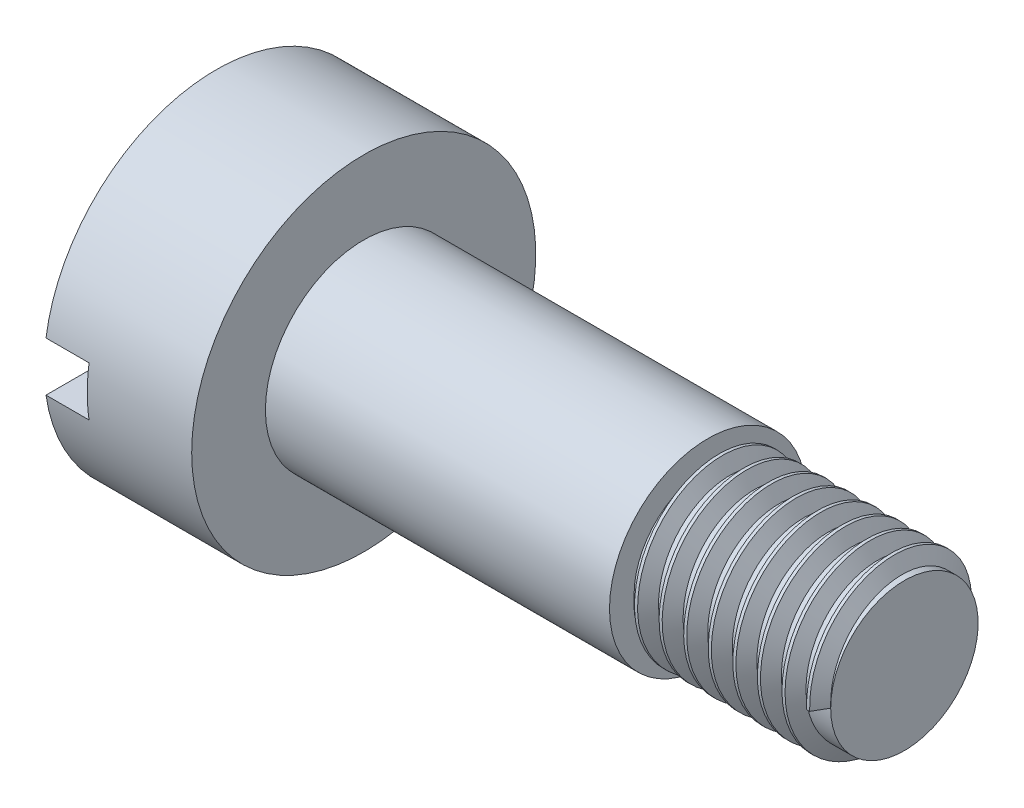
SolidWorks part; units mm, degrees
ref_plane "Front Plane" through (0, 0, 0) normal (0, 0, 1) x (1, 0, 0)
ref_plane "Top Plane" through (0, 0, 0) normal (0, 1, 0) x (1, 0, 0)
ref_plane "Right Plane" through (0, 0, 0) normal (1, 0, 0) x (0, 0, -1)
sketch "Sketch1" plane through (0, 0, 0) normal (0, 0, 1) x (1, 0, 0)
  line L0 (-7, 0) -> (7, 0)
  line L1 (-7, 0) -> (-7, 3.5)
  line L2 (-7, 3.5) -> (-4, 3.5)
  line L5 (7, 0) -> (7, 1.5)
  line L6 (-4, 3.5) -> (-4, 2)
  line L7 (-4, 2) -> (3, 2)
  line L8 (3, 2) -> (3, 1.5)
  line L9 (3, 1.5) -> (7, 1.5)
  point P3 (0, 0)
  dimension "D2" = 1.5
  dimension "D1" = 14
  dimension "D3" = 2
  dimension "D4" = 3.5
  dimension "D5" = 7
  dimension "D6" = 4
revolve "Revolve1" add sketch "Sketch1" angle 360 about L0
sketch "Sketch2" plane through (0, 0, 0) normal (0, 0, 1) x (1, 0, 0)
  line L0 (-7, 3.5) -> (-7, -3.5) construction
  line L1 (-7.8756, 0.503) -> (-6.1244, 0.503)
  line L2 (-7.8756, 0.503) -> (-7.8756, -0.503)
  line L3 (-7.8756, -0.503) -> (-6.1244, -0.503)
  line L4 (-6.1244, 0.503) -> (-6.1244, -0.503)
  line L5 (-7.8756, 0.503) -> (-6.1244, -0.503) construction
  line L6 (-7.8756, -0.503) -> (-6.1244, 0.503) construction
  point P0 (-7, 0)
  dimension "D1" = 6.1244
  dimension "D2" = 0.503
extrude "Cut-Extrude1" cut sketch "Sketch2" against normal through all both and the other way through all
thread "Thread1" pitch 0.5 method extrude profile "Thread Profile1" start angle 0, offset 0, length 0, pitch 0.5, diameter 3
ref_plane "Plane1" through (7, 0, 1.5) normal (0, -1, 0) x (0, 0, 1)
sketch "Thread Profile1" plane through (7, 0, 1.5) normal (0, -1, 0) x (0, 0, 1)
  line L0 (0, 0) -> (0, 0.5) construction
  line L1 (0, 0) -> (0.2706, 0.1562)
  line L2 (0.2706, 0.1562) -> (0.2706, 0.2187)
  line L3 (0.2706, 0.2187) -> (0, 0.375)
  line L4 (0.2706, 0.1875) -> (0, 0.1875) construction
  line L11 (0, 0) -> (0, 0.375)
  point P2 (0, 0)
  dimension "Pitch" = 0.5
  dimension "Profile_Angle" = 60
  dimension "Profile_Land" = 0.0625
  dimension "Profile_Height" = 0.2706
